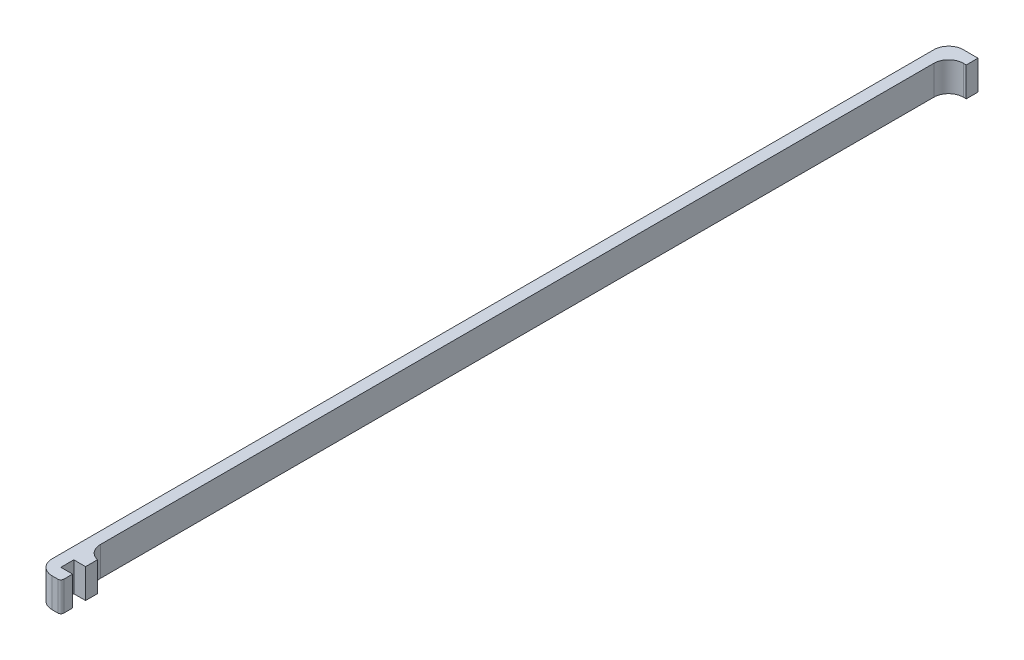
SolidWorks part; units mm, degrees
ref_plane "Front Plane" through (0, 0, 0) normal (0, 0, 1) x (1, 0, 0)
ref_plane "Top Plane" through (0, 0, 0) normal (0, 1, 0) x (1, 0, 0)
ref_plane "Right Plane" through (0, 0, 0) normal (1, 0, 0) x (0, 0, -1)
sketch "Sketch1" plane through (0, 0, 0) normal (0, 1, 0) x (1, 0, 0)
  line L1 (-19.5, 77.5) -> (19.5, 77.5)
  line L2 (-19.5, 77.5) -> (-19.5, -77.5)
  line L3 (-19.5, -77.5) -> (19.5, -77.5)
  line L4 (19.5, 77.5) -> (19.5, -77.5)
  line L5 (-19.5, 77.5) -> (19.5, -77.5) construction
  line L6 (-19.5, -77.5) -> (19.5, 77.5) construction
  point P0 (0, 0)
  dimension "D1" = 39
  dimension "D2" = 155
extrude "Boss-Extrude1" add sketch "Sketch1" along normal blind 2
sketch "Sketch2" plane through (0, 2, 0) normal (0, 1, 0) x (1, 0, 0)
  line L0 (-17.5, -75.5) -> (-17.5, -77.5)
  line L1 (-19.5, 77.5) -> (19.5, 77.5)
  line L2 (-19.5, 77.5) -> (-19.5, -77.5)
  line L3 (-19.5, -77.5) -> (19.5, -77.5)
  line L4 (19.5, 77.5) -> (19.5, -77.5)
  line L5 (-17.5, 75.5) -> (17.5, 75.5)
  line L6 (-17.5, 75.5) -> (-17.5, -75.5)
  line L7 (-17.5, -75.5) -> (17.5, -75.5)
  line L8 (17.5, 75.5) -> (17.5, -75.5)
  line L9 (-17.5, 75.5) -> (17.5, -75.5) construction
  line L10 (-17.5, -75.5) -> (17.5, 75.5) construction
  line L11 (17.5, -75.5) -> (17.5, -77.5)
  point P6 (0, 0)
  line M9 (19.5, -77.5) -> (19.5, 77.5)
  line M10 (19.5, 77.5) -> (-19.5, 77.5)
  line M11 (-19.5, 77.5) -> (-19.5, -77.5)
  line M12 (-19.5, -77.5) -> (19.5, -77.5)
  dimension "D1" = 2
  dimension "D2" = 2
extrude "Boss-Extrude2" add sketch "Sketch2" along normal blind 38 contours L8 L11 L3 L0 L6 L5 M9 M10 M11 M12 region at (-19.0983, 2, 76.5)
sketch "Sketch3" plane through (0, 2, 0) normal (0, 1, 0) x (1, 0, 0)
  line L0 (-17.5, 75.5) -> (-17.5, -77.5) construction
  line L1 (-17.5, -77.5) -> (-15.5, -77.5)
  line L2 (-17.5, -77.5) -> (-17.5, -75.5)
  line L3 (-17.5, -75.5) -> (-15.5, -75.5)
  line L4 (-15.5, -77.5) -> (-15.5, -75.5)
  line L5 (-17.5, -73.3) -> (-15.5, -73.3)
  line L6 (-17.5, -73.3) -> (-17.5, -71.3)
  line L7 (-17.5, -71.3) -> (-15.5, -71.3)
  line L8 (-15.5, -73.3) -> (-15.5, -71.3)
  line L9 (17.5, 75.5) -> (17.5, -77.5) construction
  line L10 (17.5, -77.5) -> (15.5, -77.5)
  line L11 (17.5, -77.5) -> (17.5, -75.5)
  line L12 (17.5, -75.5) -> (15.5, -75.5)
  line L13 (15.5, -77.5) -> (15.5, -75.5)
  line L14 (17.5, -73.3) -> (15.5, -73.3)
  line L15 (17.5, -73.3) -> (17.5, -71.3)
  line L16 (17.5, -71.3) -> (15.5, -71.3)
  line L17 (15.5, -73.3) -> (15.5, -71.3)
  line L18 (15.5, -75.5) -> (15.5, -73.3) construction
  line L19 (-15.5, -73.3) -> (15.5, -73.3) construction
  line L20 (-15.5, -75.5) -> (-15.5, -73.3) construction
  line L21 (-15.5, -75.5) -> (15.5, -75.5) construction
  line L22 (15.5, -71.3) -> (-15.5, -71.3) construction
  dimension "D1" = 2
  dimension "D2" = 2
  dimension "D3" = 2.2
  dimension "D4" = 2
extrude "Boss-Extrude3" add sketch "Sketch3" along normal up to surface (38 mm away) up to face at (0, 40, 0.5)
sketch "Sketch4" plane through (0, 0, -75.5) normal (0, 0, 1) x (1, 0, 0)
  line L0 (-17.5, 40) -> (-15.5, 40)
  line L1 (-17.5, 40) -> (17.5, 40) construction
  line L2 (-15.5, 40) -> (-15.5, 38)
  line L3 (-15.5, 38) -> (-17.5, 38)
  line L5 (-17.5, 38) -> (-17.5, 40)
  line L7 (-17.5, 40) -> (-17.5, 2) construction
  line L8 (-15.5, 33.8) -> (-17.5, 31.8)
  line L9 (-17.5, 31.8) -> (-17.5, 35.8)
  line L10 (-15.5, 33.8) -> (-15.5, 35.8)
  line L11 (-15.5, 35.8) -> (-17.5, 35.8)
  line L12 (0, 0) -> (0, 40) construction
  line L13 (15.5, 35.8) -> (17.5, 35.8)
  line L14 (15.5, 33.8) -> (15.5, 35.8)
  line L15 (17.5, 31.8) -> (17.5, 35.8)
  line L16 (15.5, 33.8) -> (17.5, 31.8)
  line L17 (17.5, 38) -> (17.5, 40)
  line L18 (15.5, 38) -> (17.5, 38)
  line L19 (15.5, 40) -> (15.5, 38)
  line L20 (17.5, 40) -> (15.5, 40)
  dimension "D1" = 2
  dimension "D2" = 2
  dimension "D3" = 45
  dimension "D4" = 2.2
  dimension "D5" = 2
extrude "Boss-Extrude4" add sketch "Sketch4" along normal up to surface (153 mm away)
sketch "Sketch5" plane through (0, 2, 0) normal (0, 1, 0) x (1, 0, 0)
  line L1 (-15.5, -77.5) -> (15.5, -77.5)
  line L2 (-15.5, -77.5) -> (-15.5, -75.5)
  line L3 (-15.5, -75.5) -> (15.5, -75.5)
  line L4 (15.5, -77.5) -> (15.5, -75.5)
  line L5 (-15.5, -71.3) -> (15.5, -71.3)
  line L6 (-15.5, -71.3) -> (-15.5, -73.3)
  line L7 (-15.5, -73.3) -> (15.5, -73.3)
  line L8 (15.5, -71.3) -> (15.5, -73.3)
sketch "Sketch6" plane through (0, 0, -75.5) normal (0, 0, 1) x (1, 0, 0)
  line L0 (-17.5, 38) -> (-15.5, 38) construction
  line L1 (-17.5, 38) -> (17.5, 38)
  line L2 (-17.5, 38) -> (-17.5, 35.8)
  line L3 (-17.5, 35.8) -> (17.5, 35.8)
  line L4 (17.5, 38) -> (17.5, 35.8)
  line L5 (-17.5, 38) -> (-17.5, 35.8) construction
  line L6 (-15.5, 35.8) -> (-17.5, 35.8) construction
extrude "Cut-Extrude1" cut sketch "Sketch6" along normal through all
sketch "Sketch7" plane through (0, 2, 0) normal (0, 1, 0) x (1, 0, 0)
  line L1 (-17.5, -75.5) -> (17.5, -75.5)
  line L2 (-17.5, -75.5) -> (-17.5, -73.3)
  line L3 (-17.5, -73.3) -> (17.5, -73.3)
  line L4 (17.5, -75.5) -> (17.5, -73.3)
extrude "Cut-Extrude2" cut sketch "Sketch7" along normal through all
extrude "Boss-Extrude5" add sketch "Sketch5" along normal blind 2
sketch "Sketch8" plane through (0, 0, 0) normal (1, 0, 0) x (0, 0, -1)
  line L0 (75.5, 40) -> (73.5, 40)
  line L1 (-73.3, 40) -> (75.5, 40) construction
  line L2 (73.5, 40) -> (73.5, 38)
  line L3 (-73.3, 38) -> (75.5, 38) construction
  line L4 (73.5, 38) -> (75.5, 38)
  line L5 (75.5, 38) -> (75.5, 40)
  line L6 (75.5, 35.8) -> (73.5, 35.8)
  line L7 (-73.3, 35.8) -> (75.5, 35.8) construction
  line L8 (73.5, 35.8) -> (73.5, 33.8)
  line L9 (-71.3, 33.8) -> (75.5, 33.8) construction
  line L10 (73.5, 33.8) -> (75.5, 31.8)
  line L11 (75.5, 31.8) -> (75.5, 35.8)
  dimension "D1" = 2
extrude "Boss-Extrude6" add sketch "Sketch8" along normal up to surface and the other way up to surface up to face at (17.5, 16.9, -2.1) other way up to face at (-17.5, 16.9, -2.1)
sketch "Sketch10" plane through (-17.5, 0, 0) normal (1, 0, 0) x (0, 0, -1)
  line L1 (-75.5, 35.8) -> (-77.5, 35.8)
  line L2 (-75.5, 35.8) -> (-75.5, 38)
  line L3 (-75.5, 38) -> (-77.5, 38)
  line L4 (-77.5, 35.8) -> (-77.5, 38)
  line L5 (-73.3, 40) -> (-75.5, 40)
  line L6 (-73.3, 40) -> (-73.3, 38)
  line L7 (-73.3, 38) -> (-75.5, 38)
  line L8 (-75.5, 40) -> (-75.5, 38)
  line M1 (-75.5, 40) -> (-75.5, 38)
  line M2 (-75.5, 38) -> (-77.5, 38)
  line M3 (-77.5, 38) -> (-77.5, 35.8)
  line M4 (-77.5, 35.8) -> (-75.5, 35.8)
  line M11 (-73.3, 38) -> (-73.3, 40)
  line M12 (-73.3, 40) -> (-75.5, 40)
extrude "Boss-Extrude8" add sketch "Sketch10" along normal up to surface (2 mm away) contours L2 M4 M2 M3 | L7 M11 M12 M1 region at (-17.5, 39, 74.4) region at (-17.5, 36.9, 76.5) up to face at (-15.5, 39, -0.1)
sketch "Sketch11" plane through (17.5, 0, 0) normal (-1, 0, 0) x (0, 0, 1)
  line L1 (75.5, 35.8) -> (77.5, 35.8)
  line L2 (75.5, 35.8) -> (75.5, 38)
  line L3 (75.5, 38) -> (77.5, 38)
  line L4 (77.5, 35.8) -> (77.5, 38)
  line L5 (73.3, 40) -> (75.5, 40)
  line L6 (73.3, 40) -> (73.3, 38)
  line L7 (73.3, 38) -> (75.5, 38)
  line L8 (75.5, 40) -> (75.5, 38)
  line M2 (75.5, 35.8) -> (77.5, 35.8)
  line M3 (77.5, 35.8) -> (77.5, 38)
  line M4 (77.5, 38) -> (75.5, 38)
  line M5 (75.5, 38) -> (75.5, 40)
  line M6 (75.5, 40) -> (73.3, 40)
  line M7 (73.3, 40) -> (73.3, 38)
extrude "Boss-Extrude9" add sketch "Sketch11" along normal up to surface (2 mm away) contours L2 M2 M3 M4 | L7 M7 M5 M6 region at (17.5, 36.9, 76.5) region at (17.5, 39, 74.4) up to face at (15.5, 39, -0.1)
fillet "Fillet2" radius 2.5 17 edges at (-17.5, 16.9, 71.3) (17.5, 16.9, 71.3) (19.5, 20, 77.5) (-19.5, 20, 77.5) (-19.5, 20, -77.5) (-17.5, 16.9, -75.5) (17.5, 16.9, -75.5) (19.5, 20, -77.5) (-19.5, 40, 0) (0, 40, -77.5) (19.5, 40, 0) (0, 0, -77.5) (0, 0, 77.5) (-19.5, 0, 0) (19.5, 0, 0) (-17.5, 40, 77.5) (17.5, 40, 77.5)
sketch "Sketch13" plane through (0, 0, -77.5) normal (0, 0, -1) x (-1, 0, 0)
  line L0 (15.5, 37.5) -> (15.5, 4) construction
  line L1 (-15.5, 7) -> (15.5, 7)
  line L2 (-15.5, 7) -> (-15.5, 4)
  line L3 (-15.5, 4) -> (15.5, 4)
  line L4 (15.5, 7) -> (15.5, 4)
  dimension "D1" = 3
sketch "Sketch14" plane through (0, 0, -75.5) normal (0, 0, 1) x (1, 0, 0)
  line L1 (-18.25, 9) -> (18.25, 9)
  line L2 (-18.25, 9) -> (-18.25, 1.25)
  line L3 (-18.25, 1.25) -> (18.25, 1.25)
  line L4 (18.25, 9) -> (18.25, 1.25)
  line L5 (15.5, 7) -> (-15.5, 7) construction
  line L7 (17, 0) -> (17, 2.5) construction
  line L8 (19.5, 2.5) -> (17, 2.5) construction
  line L10 (-19.5, 2.5) -> (-17, 2.5) construction
  point P20 (17, 1.25)
  point P23 (18.25, 2.5)
  point P26 (-18.25, 2.5)
  dimension "D1" = 2
extrude "Boss-Extrude10" add sketch "Sketch14" along normal blind 2
extrude "Cut-Extrude4" cut sketch "Sketch13" against normal blind 2
fillet "Fillet3" radius 2 1 edges at (0, 9, -73.5)
fillet "Fillet4" radius 0.5 12 edges at (0, 4, -77.5) (0, 7, -77.5) (15.5, 7, -76.5) (15.5, 4, -76.5) (15.5, 5.5, -77.5) (-15.5, 4, -76.5) (-15.5, 7, -76.5) (-15.5, 5.5, -77.5) (0, 7, -75.5) (-15.5, 5.5, -75.5) (0, 4, -75.5) (15.5, 5.5, -75.5)
sketch "Sketch15" plane through (0, 0, 0) normal (0, -1, 0) x (1, 0, 0)
  line L0 (0, 77.5) -> (0, 0) construction
  line L1 (-17, 77.5) -> (17, 77.5) construction
  line L2 (0, 0) -> (0, -77.5) construction
  line L4 (17, -77.5) -> (-17, -77.5) construction
  circle A0 centre (0, 38.75) radius 5.1
  circle A1 centre (0, -38.75) radius 5.1
  dimension "D1" = 10.2
extrude "Cut-Extrude5" cut sketch "Sketch15" against normal through all
sketch "Sketch16" plane through (0, 2, 0) normal (0, 1, 0) x (1, 0, 0)
  circle A0 centre (0, 38.75) radius 7.1
  circle A1 centre (0, -38.75) radius 7.1
  circle A2 centre (0, 38.75) radius 5.1 construction
  dimension "D1" = 2
extrude "Boss-Extrude11" add sketch "Sketch16" along normal blind 1
fillet "Fillet5" radius 0.5 4 edges at (0, 2, 45.85) (0, 2, -31.65) (0, 3, 45.85) (0, 3, -31.65)
sketch "Sketch12" plane through (0, 0, -75.5) normal (0, 0, 1) x (1, 0, 0)
  line L0 (0, 0) -> (0, 40) construction
  line L1 (15.5, 40) -> (-15.5, 40) construction
  line L2 (0, 20) -> (-10, 20)
  line L3 (0, 20) -> (-9.0097, 15.6612)
  line L4 (0, 20) -> (-6.2349, 12.1817)
  line L5 (0, 20) -> (-2.2252, 10.2507)
  line L6 (0, 20) -> (2.2252, 10.2507)
  line L7 (0, 20) -> (6.2349, 12.1817)
  line L8 (0, 20) -> (9.0097, 15.6612)
  line L9 (0, 20) -> (10, 20)
  line L10 (0, 20) -> (9.0097, 24.3388)
  line L11 (0, 20) -> (6.2349, 27.8183)
  line L12 (0, 20) -> (2.2252, 29.7493)
  line L13 (0, 20) -> (-2.2252, 29.7493)
  line L14 (0, 20) -> (-6.2349, 27.8183)
  line L15 (0, 20) -> (-9.0097, 24.3388)
  circle A0 centre (0, 20) radius 10
  circle A1 centre (0, 20) radius 7.5
  circle A2 centre (0, 20) radius 5
  circle A3 centre (0, 20) radius 2.5
  point P26 (0, 20)
  dimension "D1" = 20
  dimension "D2" = 2.5
  dimension "D3" = 2.5
  dimension "D4" = 2.5
  dimension "D5" = 14
extrude "Cut-Extrude3" cut sketch "Sketch12" against normal through all contours A1 L6 A0 L7 | A1 L4 A0 L5 | A1 L2 A0 L3 | A1 L14 A0 L15 | A1 L0 A0 L13 | L0 A1 L12 A0 | A1 L10 A0 L11 | A1 L8 A0 L9 | A3 L8 A2 L9 | A3 L10 A2 L11 | L0 A3 L12 A2 | A3 L0 A2 L13 | A3 L14 A2 L15 | A3 L2 A2 L3 | A3 L4 A2 L5 | A3 L6 A2 L7 region at (-3.7903, 12.1293, -75.5) region at (3.7903, 12.1293, -75.5) region at (-1.6732, 16.5256, -75.5) region at (1.6732, 16.5256, -75.5) region at (-8.5168, 18.0561, -75.5) region at (8.5168, 18.0561, -75.5) region at (-0.4345, 23.8563, -75.5) region at (0.4345, 23.8563, -75.5) region at (-3.7596, 19.1419, -75.5) region at (3.7596, 19.1419, -75.5) region at (3.015, 22.4044, -75.5) region at (-3.015, 22.4044, -75.5) region at (-6.8299, 25.4467, -75.5) region at (6.8299, 25.4467, -75.5) region at (-0.9843, 28.7358, -75.5) region at (0.9843, 28.7358, -75.5)
fillet "Fillet6" radius 0.4 112 edges at (5.4555, 26.841, -77.5) (7.8183, 26.2349, -77.5) (7.8835, 23.7965, -77.5) (5.8637, 24.6762, -77.5) (3.75, 20, -77.5) (4.8746, 18.8874, -77.5) (3.3786, 18.3729, -77.5) (2.4373, 19.4437, -77.5) (-1.9471, 28.5306, -77.5) (0, 30, -77.5) (1.9471, 28.5306, -77.5) (0, 27.5, -77.5) (-7.8835, 16.2035, -77.5) (-9.7493, 17.7748, -77.5) (-8.75, 20, -77.5) (-7.312, 18.3311, -77.5) (2.3381, 17.0681, -77.5) (2.1694, 15.4952, -77.5) (0.8345, 16.344, -77.5) (1.0847, 17.7476, -77.5) (-0.8345, 16.344, -77.5) (-2.1694, 15.4952, -77.5) (-2.3381, 17.0681, -77.5) (-1.0847, 17.7476, -77.5) (5.4555, 13.159, -77.5) (4.3388, 10.9903, -77.5) (1.9471, 11.4694, -77.5) (3.2541, 13.2427, -77.5) (0, 22.5, -77.5) (-0.8345, 23.656, -77.5) (0, 25, -77.5) (0.8345, 23.656, -77.5) (-3.3786, 21.6271, -77.5) (-3.9092, 23.1174, -77.5) (-2.3381, 22.9319, -77.5) (-1.9546, 21.5587, -77.5) (-3.3786, 18.3729, -77.5) (-4.8746, 18.8874, -77.5) (-3.75, 20, -77.5) (-2.4373, 19.4437, -77.5) (-1.9471, 11.4694, -77.5) (-4.3388, 10.9903, -77.5) (-5.4555, 13.159, -77.5) (-3.2541, 13.2427, -77.5) (-7.8835, 23.7965, -77.5) (-7.8183, 26.2349, -77.5) (-5.4555, 26.841, -77.5) (-5.8637, 24.6762, -77.5) (2.3381, 22.9319, -77.5) (3.9092, 23.1174, -77.5) (3.3786, 21.6271, -77.5) (1.9546, 21.5587, -77.5) (8.75, 20, -77.5) (9.7493, 17.7748, -77.5) (7.8835, 16.2035, -77.5) (7.312, 18.3311, -77.5) (7.8835, 23.7965, -75.5) (7.8183, 26.2349, -75.5) (5.4555, 26.841, -75.5) (5.8637, 24.6762, -75.5) (3.3786, 18.3729, -75.5) (4.8746, 18.8874, -75.5) (3.75, 20, -75.5) (2.4373, 19.4437, -75.5) (1.9471, 28.5306, -75.5) (0, 30, -75.5) (-1.9471, 28.5306, -75.5) (0, 27.5, -75.5) (-8.75, 20, -75.5) (-9.7493, 17.7748, -75.5) (-7.8835, 16.2035, -75.5) (-7.312, 18.3311, -75.5) (0.8345, 16.344, -75.5) (2.1694, 15.4952, -75.5) (2.3381, 17.0681, -75.5) (1.0847, 17.7476, -75.5) (-2.3381, 17.0681, -75.5) (-2.1694, 15.4952, -75.5) (-0.8345, 16.344, -75.5) (-1.0847, 17.7476, -75.5) (1.9471, 11.4694, -75.5) (4.3388, 10.9903, -75.5) (5.4555, 13.159, -75.5) (3.2541, 13.2427, -75.5) (0, 22.5, -75.5) (0.8345, 23.656, -75.5) (0, 25, -75.5) (-0.8345, 23.656, -75.5) (-2.3381, 22.9319, -75.5) (-3.9092, 23.1174, -75.5) (-3.3786, 21.6271, -75.5) (-1.9546, 21.5587, -75.5) (-3.75, 20, -75.5) (-4.8746, 18.8874, -75.5) (-3.3786, 18.3729, -75.5) (-2.4373, 19.4437, -75.5) (-5.4555, 13.159, -75.5) (-4.3388, 10.9903, -75.5) (-1.9471, 11.4694, -75.5) (-3.2541, 13.2427, -75.5) (-5.4555, 26.841, -75.5) (-7.8183, 26.2349, -75.5) (-7.8835, 23.7965, -75.5) (-5.8637, 24.6762, -75.5) (3.3786, 21.6271, -75.5) (3.9092, 23.1174, -75.5) (2.3381, 22.9319, -75.5) (7.8835, 16.2035, -75.5) (9.7493, 17.7748, -75.5) (8.75, 20, -75.5) (7.312, 18.3311, -75.5) (1.9546, 21.5587, -75.5)
fillet "Fillet7" radius 0.5 8 edges at (15.5, 40, 0.75) (15.5, 39.2678, 76.7678) (-15.5, 40, 0.75) (-15.5, 39.2678, 76.7678) (0, 40, -73.5) (15.5, 20.75, 77.5) (-15.5, 20.75, 77.5) (0, 4, 77.5)
sketch "Sketch17" plane through (0, 0, 0) normal (0, -1, 0) x (1, 0, 0)
  line L0 (-17, -77.5) -> (-17, 70.3)
  line L1 (-17, -77.5) -> (17, -77.5)
  line L2 (17, -77.5) -> (17, 70.3)
  line L3 (17, -75) -> (17, 75) construction
  line L5 (17, 70.3) -> (15, 71.3)
  line L6 (15, 71.3) -> (15, 77.5)
  line L7 (15, 77.5) -> (-15, 77.5)
  line L8 (-15, 77.5) -> (-15, 71.3)
  line L9 (-15, 71.3) -> (-17, 70.3)
  line L10 (-17, 75) -> (-17, -75) construction
  line L12 (-15, 71.3) -> (15, 71.3) construction
  line L13 (17, 70.3) -> (-17, 70.3) construction
  line L14 (0, 71.3) -> (0, 77.5) construction
  line L15 (-17, 77.5) -> (17, 77.5) construction
  arc A0 (-19.5, -75) -> (-17, -77.5) centre (-17, -75) ccw construction
  dimension "D1" = 1
  dimension "D2" = 30
  dimension "D3" = 6.2
extrude "Cut-Extrude6" cut sketch "Sketch17" against normal blind 6
sketch "Sketch18" plane through (0, 0, 0) normal (0, 0, 1) x (1, 0, 0)
  line L0 (15, 9) -> (-15, 9) construction
  line L1 (-14.5, 9) -> (14.5, 9)
  line L2 (-14.5, 9) -> (-14.5, 6)
  line L3 (-14.5, 6) -> (14.5, 6)
  line L4 (14.5, 9) -> (14.5, 6)
  line L5 (-17, 6) -> (17, 6) construction
  line L6 (0, 6) -> (0, 0) construction
  dimension "D1" = 29
extrude "Cut-Extrude8" cut sketch "Sketch18" against normal through all
sketch "Sketch20" plane through (0, 0, 0) normal (0, 0, 1) x (1, 0, 0)
  line L0 (-16, 40) -> (16, 40) construction
  line L1 (-19.5, 40) -> (-14.5, 40)
  line L2 (-19.5, 40) -> (-19.5, 0)
  line L3 (-19.5, 0) -> (-14.5, 0)
  line L4 (-14.5, 40) -> (-14.5, 0)
  line L5 (-14.5, 6) -> (14.5, 6)
  line L6 (-14.5, 6) -> (-14.5, 40)
  line L7 (-14.5, 40) -> (14.5, 40)
  line L8 (14.5, 6) -> (14.5, 40)
  line L9 (14.5, 40) -> (19.5, 40)
  line L10 (14.5, 40) -> (14.5, 0)
  line L11 (14.5, 0) -> (19.5, 0)
  line L12 (19.5, 40) -> (19.5, 0)
  line L13 (-15, 0) -> (-17, 0) construction
  line L14 (-19.5, 2.5) -> (-19.5, 37.5) construction
  line L15 (17, 0) -> (15, 0) construction
  line L16 (19.5, 37.5) -> (19.5, 2.5) construction
extrude "Cut-Extrude11" cut sketch "Sketch20" against normal through all both and the other way through all contours L5 L8 L7 L4 | L12 L9 L8 L10 L11 region at (0, 23, 0) region at (17, 20, 0)
sketch "Sketch21" plane through (0, 0, 0) normal (1, 0, 0) x (0, 0, -1)
  line L0 (77.5, 37.5) -> (77.5, 7.5) construction
  line L1 (-77.5, 40) -> (77.5, 40)
  line L2 (-77.5, 40) -> (-77.5, 30)
  line L3 (-77.5, 30) -> (77.5, 30)
  line L4 (77.5, 40) -> (77.5, 30)
  line L5 (77.5, 30) -> (-77.5, 30)
  line L6 (77.5, 30) -> (77.5, 10)
  line L7 (77.5, 10) -> (-77.5, 10)
  line L8 (-77.5, 30) -> (-77.5, 10)
  line L9 (-77.5, 10) -> (77.5, 10)
  line L10 (-77.5, 10) -> (-77.5, 0)
  line L11 (-77.5, 0) -> (77.5, 0)
  line L12 (77.5, 10) -> (77.5, 0)
  line L13 (-70.3, 0) -> (75, 0) construction
  line L14 (-77.5, 3.5) -> (-77.5, 2.5) construction
  line L15 (-75, 40) -> (74, 40) construction
  line L16 (77.5, 30) -> (77.5, 10)
  line L17 (-77.5, 10) -> (-77.5, 30)
  dimension "D1" = 20
  dimension "D2" = 10
extrude "Cut-Extrude12" cut sketch "Sketch21" against normal through all contours L4 L1 L2 L3 | L12 L7 L10 L11 region at (0, 35, 0) region at (0, 5, 0)
sketch "Sketch22" plane through (-19.5, 0, 0) normal (-1, 0, 0) x (0, 0, 1)
  line L0 (77.5, 30) -> (77.5, 10) construction
  line L1 (-77.5, 10) -> (77.5, 10)
  line L2 (-77.5, 10) -> (-77.5, 25)
  line L3 (-77.5, 25) -> (77.5, 25)
  line L4 (77.5, 10) -> (77.5, 25)
  line L5 (75, 30) -> (-75, 30) construction
  dimension "D1" = 5
extrude "Cut-Extrude13" cut sketch "Sketch22" against normal through all
